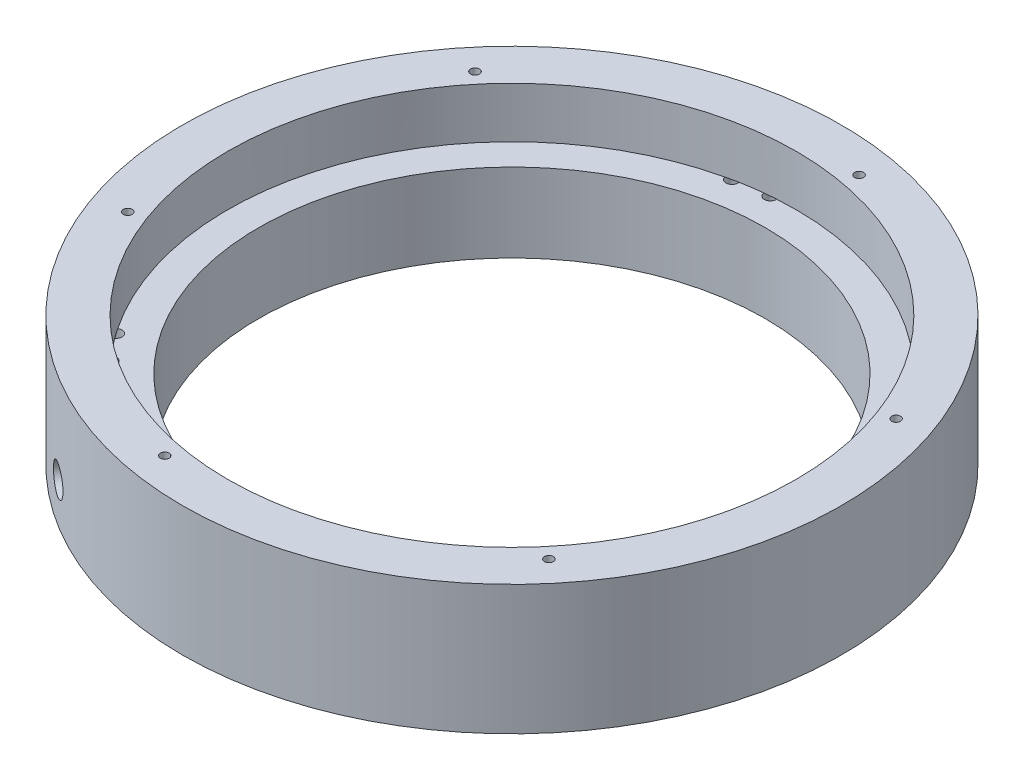
SolidWorks part; units mm, degrees
material "6061 Alloy"
ref_plane "Front Plane" through (0, 0, 0) normal (0, 0, 1) x (1, 0, 0)
ref_plane "Top Plane" through (0, 0, 0) normal (0, 1, 0) x (1, 0, 0)
ref_plane "Right Plane" through (0, 0, 0) normal (1, 0, 0) x (0, 0, -1)
sketch "Sketch1" plane through (0, 0, 0) normal (0, 1, 0) x (1, 0, 0)
  line L0 (26.7963, -63.1282) -> (0, 0) construction
  line L1 (0, 0) -> (0, -32.7983) construction
  line L2 (0, 0) -> (58.126, -27.1046) construction
  line L3 (0, 0) -> (-15.1655, -86.0079) construction
  line L4 (0, 0) -> (84.7676, -52.9687) construction
  circle A0 centre (0, 0) radius 57.15
  circle A1 centre (0, 0) radius 74.3712
  circle A3 centre (0, 0) radius 64.135
  circle A4 centre (-11.7434, -66.6001) radius 1.0033
  circle A5 centre (26.7963, -63.1282) radius 1.9939
  circle A6 centre (26.7963, -63.1282) radius 5.5626
  circle A7 centre (58.126, -27.1046) radius 1.3589
  circle A8 centre (60.9305, -20.0194) radius 1.3589
  dimension "D1" = 114.3
  dimension "D5" = 2.0066
  dimension "D7" = 3.9878
  dimension "D9" = 11.1252
  dimension "D10" = 2.7178
  dimension "D2" = 148.7424
  dimension "D4" = 67.6275
  dimension "D6" = 68.58
  dimension "D8" = 23
  dimension "D11" = 65
  dimension "D15" = 58
  dimension "D12" = 7.62
  dimension "D13" = 10
  dimension "D3" = 6.985
extrude "Boss-Extrude1" add sketch "Sketch1" along normal blind 17.78 contours A7 A3 A6 A0 | A3 A6 A5 | A5 | A3 A6 | A1 A7 A3 A6 A4 | A3 A7 | A3 A7 | A3 A8 | A3 A8 region at (-72.2677, 0, 0) region at (61.6385, 0, 9.1979) region at (24.877, 0, 58.6065) region at (25.1207, 0, 59.1805) region at (61.4759, 0, 20.1987) region at (60.3801, 0, 19.8386) region at (57.601, 0, 26.8598) region at (58.6464, 0, 27.3473) region at (26.7963, 0, 63.1282)
extrude "Boss-Extrude3" add sketch "Sketch1<3>" along normal blind 11.43 from surface contours A1 A7 A3 A6 A4 | A3 A6 A5 | A5 | A3 A7 | A3 A8 region at (-72.2677, 0, 0) region at (25.1207, 0, 59.1805) region at (61.4759, 0, 20.1987) region at (58.6464, 0, 27.3473) region at (26.7963, 0, 63.1282) starting at face at (0, 17.78, 57.15)
sketch "Sketch1<3>" plane through (0, 0, 0) normal (0, 1, 0) x (1, 0, 0) same geometry as "Sketch1"
pattern_circular "CirPattern1" count 6 over 360 about axis through (0, 29.21, 0) along (0, 1, 0) of face at (-11.7434, 0, 67.6034)
sketch "Sketch2" plane through (0, 0, 0) normal (1, 0, 0) x (0, 0, -1)
  line L0 (-57.15, 0) -> (57.15, 0) construction
  line L1 (57.15, 17.78) -> (-57.15, 17.78) construction
  line L2 (-57.15, 0) -> (57.15, 0)
  line L3 (57.15, 17.78) -> (-57.15, 17.78)
  line L4 (91.6697, 17.018) -> (97.1828, 17.018) construction
  line L5 (0, 17.78) -> (0, 35.8369)
  circle A0 centre (60.6425, 18.6055) radius 1.5875 construction
  circle A1 centre (60.6425, 18.669) radius 1.651
  dimension "D2" = 3.175
  dimension "D4" = 3.302
  dimension "D1" = 60.6425
  dimension "D3" = 0.762
extrude "Cut-Extrude2" cut sketch "Sketch1<4>" along normal blind 0.635 contours A3 A6 A5 | A3 A6 | A6 region at (24.877, 0, 58.6065) region at (25.1207, 0, 59.1805)
sketch "Sketch1<4>" plane through (0, 0, 0) normal (0, 1, 0) x (1, 0, 0) same geometry as "Sketch1"
extrude "Cut-Extrude3" cut sketch "Sketch1<5>" along normal blind 6.35 contours A5 region at (26.7963, 0, 63.1282)
sketch "Sketch1<5>" plane through (0, 0, 0) normal (0, 1, 0) x (1, 0, 0) same geometry as "Sketch1"
pattern_circular "CirPattern3" count 3 over 360 about axis through (0, 0, 0) along (0, 1, 0) of face at (26.7963, 6.35, 65.1221) of face at (26.7963, 6.35, 65.1221) of face at (26.7963, 0.635, 65.1221) of face at (26.7963, 0.635, 68.6908)
ref_plane "Plane1" through (0, 0, 0) normal (-0.5299, 0, 0.848) x (0.848, 0, 0.5299)
sketch "Sketch3" plane through (0, 0, 0) normal (-0.5299, 0, 0.848) x (0.848, 0, 0.5299)
  line L0 (57.15, 17.78) -> (-57.15, 17.78) construction
  line L1 (57.15, 17.78) -> (-57.15, 17.78)
  line L2 (0, 0) -> (0, 17.78) construction
  circle A0 centre (0, 8.89) radius 3.3528
  circle A1 centre (0, 8.89) radius 3.9751
  dimension "D1" = 6.7056
  dimension "D3" = 7.9502
  dimension "D2" = 8.89
extrude "Cut-Extrude5" cut sketch "Sketch3" along normal up to surface (74.2956 mm away) contours L2 A0 | A0 L2 region at (-1.2067, 8.89, -0.7541) region at (1.2067, 8.89, 0.7541) up to face at (0, 0, 74.3712)
extrude "Cut-Extrude13" cut sketch "Sketch1<6>" along normal up to surface (17.78 mm away) contours A3 A8 | A3 A8 | A7 region at (61.4759, 0, 20.1987) region at (60.3801, 0, 19.8386) up to face at (0, 17.78, 57.15)
sketch "Sketch1<6>" plane through (0, 0, 0) normal (0, 1, 0) x (1, 0, 0) same geometry as "Sketch1"
pattern_circular "CirPattern4" count 3 over 360 about axis through (0, 0, 0) along (0, 1, 0) of "Cut-Extrude13"
equation "\"Middle Coupler Inner Daimeter\"= 3.875in"
equation "\"Middle Coupler  Wall Thickness\" = 0.25in"
equation "\"Middle Coupler Bottom Thickness\"= 0.2in"
equation "\"Bearing Rail Offset\"= 0.45in"
equation "\"3-56 UNF Tap\"= 0.089in"
equation "\"3-56 UNF Clearance\"= 0.104in"
equation "\"Ball Bearing Distance\"= 0.03in"
equation "\"D1@Sketch1\"=\"Middle Coupler Inner Daimeter\"+0.625in"
equation "\"D3@Sketch1\"=0.275"
equation "\"D4@Sketch1\"=\"Middle Coupler Inner Daimeter\"/2+0.625/2+0.275+0.275/2"
equation "\"D5@Sketch1\"=\"3-48 Tap\""
equation "\"D1@Sketch2\"=\"Middle Coupler Inner Daimeter\"/2in + \"Bearing Rail Offset\""
equation "\"D3@Sketch2\"=\"Ball Bearing Distance\""
equation "\"D4@Sketch2\"=\"D2@Sketch2\"+0.005"
equation "\"D1@Boss-Extrude3\"=0.320in+0.01in + 0.03*4"
equation "\"TCA Outer Diameter\" = 6in"
equation "\"Interstage Aeroframe Wall Thickness\" = 0.072in"
equation "\"Compression Spring OD\"= 0.42in"
equation "\"10-24 Tap\"= 0.157in"
equation "\"10-24 Clearance\"= 0.196in"
equation "\"Lower Stage Fuselage Wall Thickness\" = 0.25in"
equation "\"6-32 Tap\" = 0.107in"
equation "\"D10@Sketch1\"=\"6-32 Tap\""
equation "\"1/4-20 Tap\" = 0.201in"
equation "\"D1@Sketch3\"=0.254 + 0.01"
equation "\"12-24 Tap\" = 0.177in"
equation "\"D3@Sketch3\"=0.313"
equation "\"3-48 Tap\"= 0.079in"
equation "\"3-48 Clearance\" = 0.104in"
equation "\"6-32 Clearance\" = 0.144"
equation "\"D2@Sketch1\"=\"TCA Outer Diameter\"-\"Interstage Aeroframe Wall Thickness\"*2"
equation "\"D6@Sketch1\"=(\"Middle Coupler Inner Daimeter\"+\"TCA Outer Diameter\"+0.5+0.0125*2in)/4 + 0.1"
